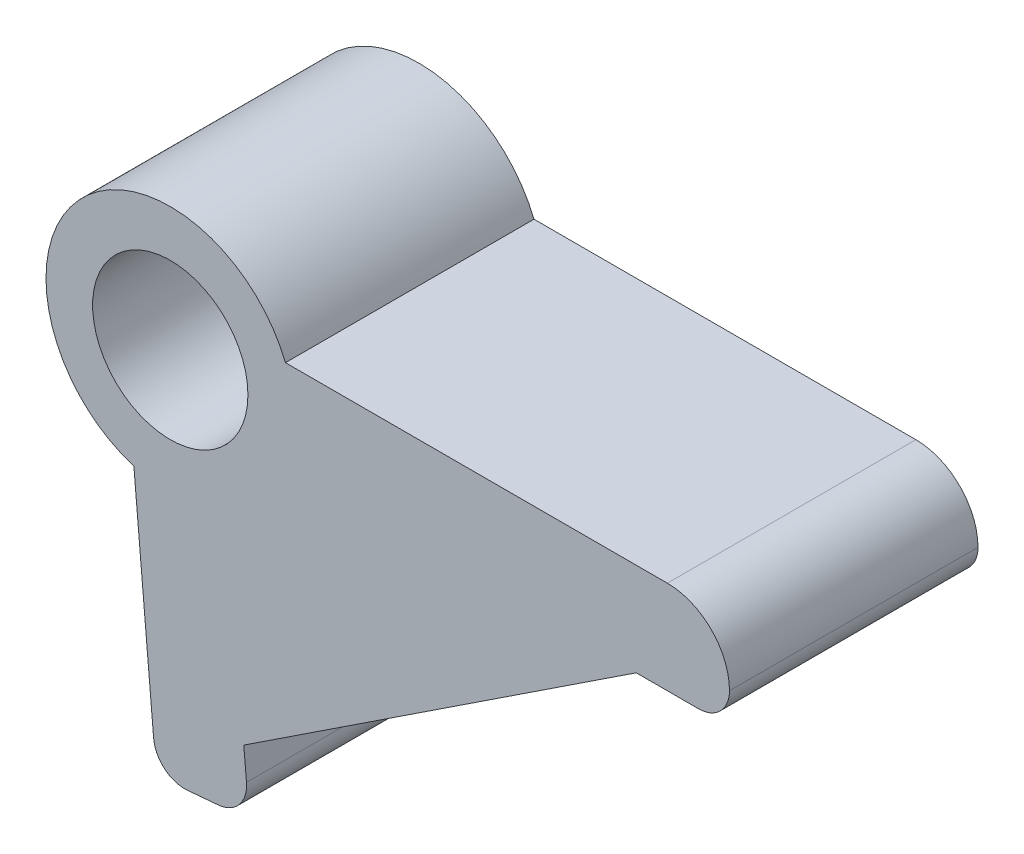
SolidWorks part; units mm, degrees
ref_plane "Front Plane" through (0, 0, 0) normal (0, 0, 1) x (1, 0, 0)
ref_plane "Top Plane" through (0, 0, 0) normal (0, 1, 0) x (1, 0, 0)
ref_plane "Right Plane" through (0, 0, 0) normal (1, 0, 0) x (0, 0, -1)
sketch "Sketch1" plane through (0, 0, 0) normal (0, 0, 1) x (1, 0, 0)
  line L0 (0, 0) -> (0, 10.942) construction
  line L1 (0, 0) -> (1.0459, -11.9543) construction
  line L2 (1.0459, -11.9543) -> (-0.4484, -12.0851)
  line L3 (-0.4484, -12.0851) -> (-1.1711, -3.8247)
  line L5 (1.8175, -3.5633) -> (2.5402, -11.8236)
  line L6 (2.5402, -11.8236) -> (1.0459, -11.9543)
  line L7 (0, 0) -> (18, 0) construction
  line L8 (15, -1.5) -> (2.3658, -9.8312)
  line L9 (3.7081, 1.5) -> (18, 1.5)
  line L11 (3.7081, -1.5) -> (18, -1.5)
  line L12 (18, 1.5) -> (18, -1.5)
  circle A0 centre (0, 0) radius 2.5
  arc A1 (3.7081, 1.5) -> (-1.1711, -3.8247) centre (0, 0) ccw
  arc A2 (1.8175, -3.5633) -> (3.7081, -1.5) centre (0, 0) ccw
  dimension "D1" = 5
  dimension "D6" = 8
  dimension "D2" = 18
  dimension "D3" = 12
  dimension "D4" = 3
  dimension "D5" = 3
  dimension "D7" = 85
  dimension "D8" = 3
  dimension "D9" = 2
extrude "Boss-Extrude1" add sketch "Sketch1" along normal blind 8 contours A2 L5 L8 L11 | A0 | L2 L3 A1 L9 L12 L11 A2 L5 L6 region at (6.5245, -4.3762, 0) region at (0, 0, 0)
fillet "Fillet1" radius 1 3 edges at (-0.4484, -12.0851, 4) (2.5402, -11.8236, 4) (18, -1.5, 4)
fillet "Fillet2" radius 2 1 edges at (18, 1.5, 4)
